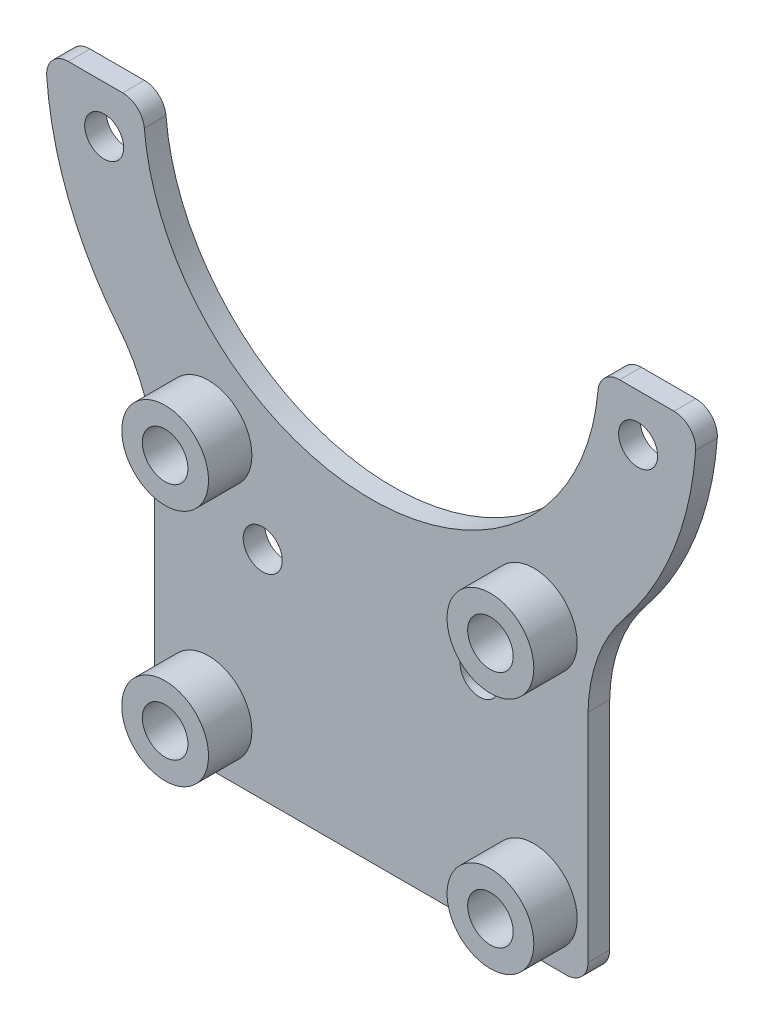
SolidWorks part; units mm, degrees
ref_plane "Płaszczyzna przednia" through (0, 0, 0) normal (0, 0, 1) x (1, 0, 0)
ref_plane "Płaszczyzna górna" through (0, 0, 0) normal (0, 1, 0) x (1, 0, 0)
ref_plane "Płaszczyzna prawa" through (0, 0, 0) normal (1, 0, 0) x (0, 0, -1)
sketch "Sketch1" plane through (0, 0, 0) normal (0, 0, 1) x (1, 0, 0)
  line L0 (0, -39) -> (0, 0) construction
  line L1 (-20, -28) -> (20, -28)
  line L2 (-20, -28) -> (-20, -50)
  line L3 (-20, -50) -> (20, -50)
  line L4 (20, -28) -> (20, -50)
  line L5 (-20, -28) -> (20, -50) construction
  line L6 (-20, -50) -> (20, -28) construction
  line L7 (-30, 0) -> (30, 0)
  circle A0 centre (0, 0) radius 30
  circle A1 centre (0, 0) radius 21
  point P3 (0, -39)
  dimension "D1" = 60
  dimension "D5" = 42
  dimension "D2" = 28
  dimension "D3" = 40
  dimension "D4" = 22
extrude "Boss-Extrude1" add sketch "Sketch1" along normal blind 2 contours A0 L1 L2 L3 L4 | L1 A0 | L1 A0
fillet "Fillet1" radius 15 2 edges at (-10.7703, -28, 1) (10.7703, -28, 1)
fillet "Fillet3" radius 2 6 edges at (20, -50, 1) (-20, -50, 1) (-30, 0, 1) (30, 0, 1) (-21, 0, 1) (21, 0, 1)
hole_wizard "M3 Clearance Hole1" positions "Sketch5" profile "Sketch6" hole size "M3" standard "DIN" end condition up to next
sketch "Sketch5" plane through (0, 0, 2) normal (0, 0, 1) x (1, 0, 0)
  line L3 (0, 0) -> (-25, 0) construction
  line L5 (0, 0) -> (-24.6202, -4.3412) construction
  line L7 (0, 0) -> (0, -30) construction
  line L8 (0, -30) -> (-10, -30) construction
  circle A1 centre (0, 0) radius 25 construction
  circle A2 centre (-24.6202, -4.3412) radius 5 construction
  point P21 (-24.6202, -4.3412)
  point P31 (-10, -30)
  point P39 (24.6202, -4.3412)
  point P40 (10, -30)
  point P41 (0, 0)
  point P42 (0, 0)
  dimension "D1" = 10
  dimension "D2" = 10
  dimension "D5" = 50
  dimension "D3" = 10
  dimension "D4" = 30
sketch "Sketch6" plane through (10, -30, 2) normal (1, 0, 0) x (0, -1, 0)
  line L0 (0, 0) -> (0, 2)
  line L1 (0, 2) -> (1.8, 2)
  line L2 (1.8, 2) -> (1.8, 0)
  line L5 (1.8, 0) -> (0, 0)
  line L11 (0, -6.35) -> (0, 107.95) construction
  dimension "Thru Hole Dia." = 3.6
  dimension "Thru Hole Depth" = 2
sketch "Sketch7" plane through (0, 0, 2) normal (0, 0, 1) x (1, 0, 0)
  line L0 (0, -45) -> (0, -50) construction
  line L1 (-15, -45) -> (15, -45) construction
  line L2 (-15, -45) -> (-15, -23) construction
  line L3 (-15, -23) -> (15, -23) construction
  line L4 (15, -45) -> (15, -23) construction
  line L5 (-18, -50) -> (18, -50) construction
  circle A0 centre (-15, -45) radius 4
  circle A1 centre (15, -45) radius 4
  circle A2 centre (15, -23) radius 4
  circle A3 centre (-15, -23) radius 4
  dimension "D1" = 8
  dimension "D2" = 5
  dimension "D3" = 22
  dimension "D4" = 30
extrude "Boss-Extrude2" add sketch "Sketch7" along normal blind 4
hole_wizard "Ø4.2 (4.2) Diameter Hole1" positions "Sketch8" profile "Sketch10" hole size "Ø4.2" standard "DIN" end condition through all
sketch "Sketch8" plane through (0, 0, 6) normal (0, 0, 1) x (1, 0, 0)
  point P0 (-15, -23)
  point P3 (15, -23)
  point P6 (15, -45)
  point P9 (-15, -45)
sketch "Sketch10" plane through (-15, -23, 6) normal (1, 0, 0) x (0, -1, 0)
  line L0 (0, 0) -> (0, 6)
  line L1 (0, 6) -> (2.1, 6)
  line L2 (2.1, 6) -> (2.1, 0)
  line L5 (2.1, 0) -> (0, 0)
  line L11 (0, -6.35) -> (0, 107.95) construction
  dimension "Thru Hole Dia." = 4.2
  dimension "Thru Hole Depth" = 6
